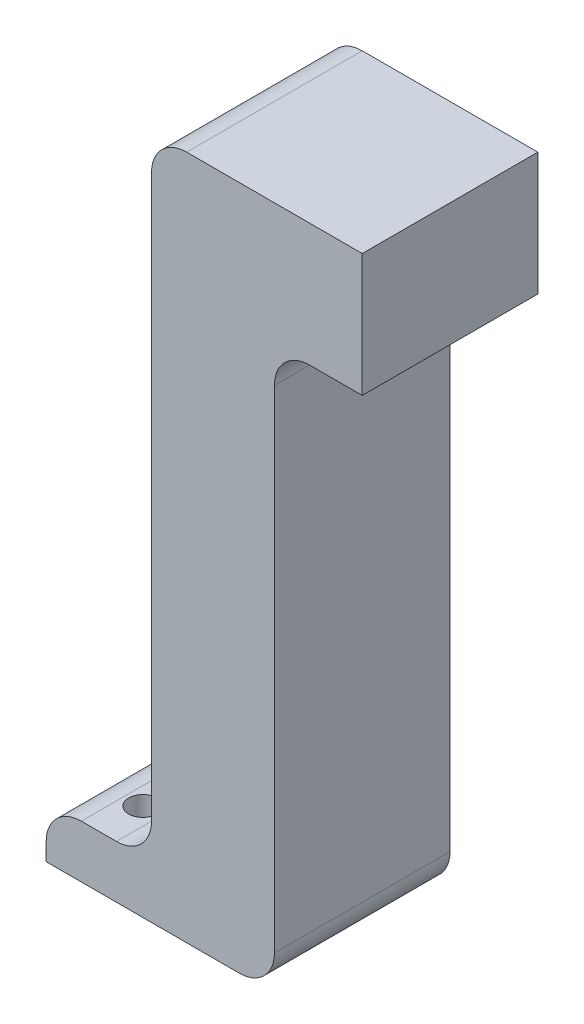
SolidWorks part; units mm, degrees
ref_plane "Front Plane" through (0, 0, 0) normal (0, 0, 1) x (1, 0, 0)
ref_plane "Top Plane" through (0, 0, 0) normal (0, 1, 0) x (1, 0, 0)
ref_plane "Right Plane" through (0, 0, 0) normal (1, 0, 0) x (0, 0, -1)
sketch "Sketch1" plane through (0, 0, 0) normal (0, 0, 1) x (1, 0, 0)
  line L0 (-1.4642, 0.25) -> (-1.4642, -7.75)
  line L5 (-1.4642, 0.25) -> (1.5358, 0.25)
  line L6 (-1.4642, 0.25) -> (-1.4642, 2)
  line L7 (-1.4642, 2) -> (1.5358, 2)
  line L8 (1.5358, 0.25) -> (1.5358, 2)
  line L9 (-1.4642, -7.75) -> (-2.9642, -7.75)
  line L10 (-1.4642, -7.75) -> (-1.4642, -7)
  line L11 (-1.4642, -7) -> (-2.9642, -7)
  line L12 (-2.9642, -7.75) -> (-2.9642, -7)
  line L13 (-1.4642, 0.25) -> (0.2858, 0.25)
  line L14 (-1.4642, -7.75) -> (0.2858, -7.75)
  line L15 (0.2858, 0.25) -> (0.2858, -7.75)
  dimension "D1" = 1.75
  dimension "D2" = 3
  dimension "D3" = 0
  dimension "D4" = 1.75
  dimension "D5" = 0.75
  dimension "D6" = 8
  dimension "D7" = 1.5
extrude "Boss-Extrude1" add sketch "Sketch1" along normal blind 1.875 and the other way blind 0.625 contours L5 L8 L7 L6 | L12 L9 L0 L11 | L13 L15 L14 L0 region at (0.0358, 1.125, 0) region at (-2.2142, -7.375, 0)
fillet "Fillet1" radius 0.5 5 edges at (0.2858, 0.25, 0.625) (-1.4642, 2, 0.625) (-2.9642, -7, 0.625) (0.2858, -7.75, 0.625) (-1.4642, -7, 0.625)
hole_wizard "Ø0.4 (0.4) Diameter Hole1" positions "Sketch2" profile "Sketch3" hole size "Ø0.4" standard "DIN" end condition through all
sketch "Sketch2" plane through (0, -7, 0) normal (0, 1, 0) x (1, 0, 0)
  line L0 (-1.4642, 0) -> (-2.9642, 0) construction
  point P0 (-2.2142, 0)
  point P4 (-2.2142, -1.25)
  dimension "D1" = 1.25
sketch "Sketch3" plane through (-2.2142, -7, 0) normal (1, 0, 0) x (0, 0, 1)
  line L0 (0, 0) -> (0, 0.75)
  line L1 (0, 0.75) -> (0.2, 0.75)
  line L2 (0.2, 0.75) -> (0.2, 0)
  line L5 (0.2, 0) -> (0, 0)
  line L11 (0, -6.35) -> (0, 107.95) construction
  dimension "Thru Hole Dia." = 0.4
  dimension "Thru Hole Depth" = 0.75
